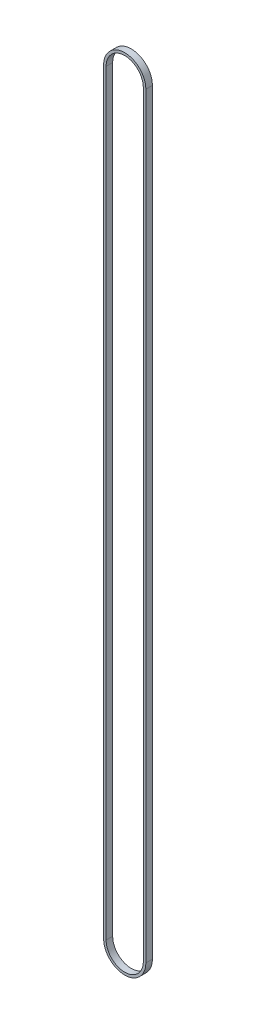
SolidWorks part; units mm, degrees
material "Cast Alloy Steel"
ref_plane "Front Plane" through (0, 0, 0) normal (0, 0, 1) x (1, 0, 0)
ref_plane "Top Plane" through (0, 0, 0) normal (0, 1, 0) x (1, 0, 0)
ref_plane "Right Plane" through (0, 0, 0) normal (1, 0, 0) x (0, 0, -1)
sketch "Sketch1" plane through (0, 0, 0) normal (0, 0, 1) x (1, 0, 0)
  line L0 (-25.1587, 901.7) -> (-25.1587, 0)
  line L1 (25.1587, 0) -> (25.1587, 901.7)
  line L2 (22.1615, 0) -> (22.1615, 901.7)
  line L3 (-22.1615, 901.7) -> (-22.1615, 0)
  circle A0 centre (0, 0) radius 25.1587 construction
  circle A1 centre (0, 901.7) radius 25.1587 construction
  arc A2 (-25.1587, 901.7) -> (25.1587, 901.7) centre (0, 901.7) cw
  arc A3 (-25.1587, 0) -> (25.1587, 0) centre (0, 0) ccw
  arc A4 (-22.1615, 901.7) -> (22.1615, 901.7) centre (0, 901.7) cw
  arc A5 (-22.1615, 0) -> (22.1615, 0) centre (0, 0) ccw
  dimension "D2" = 50.3174
  dimension "D1" = 901.7
  dimension "D3" = 2.9972
extrude "Boss-Extrude1" add sketch "Sketch1" along normal mid plane 7.7978
